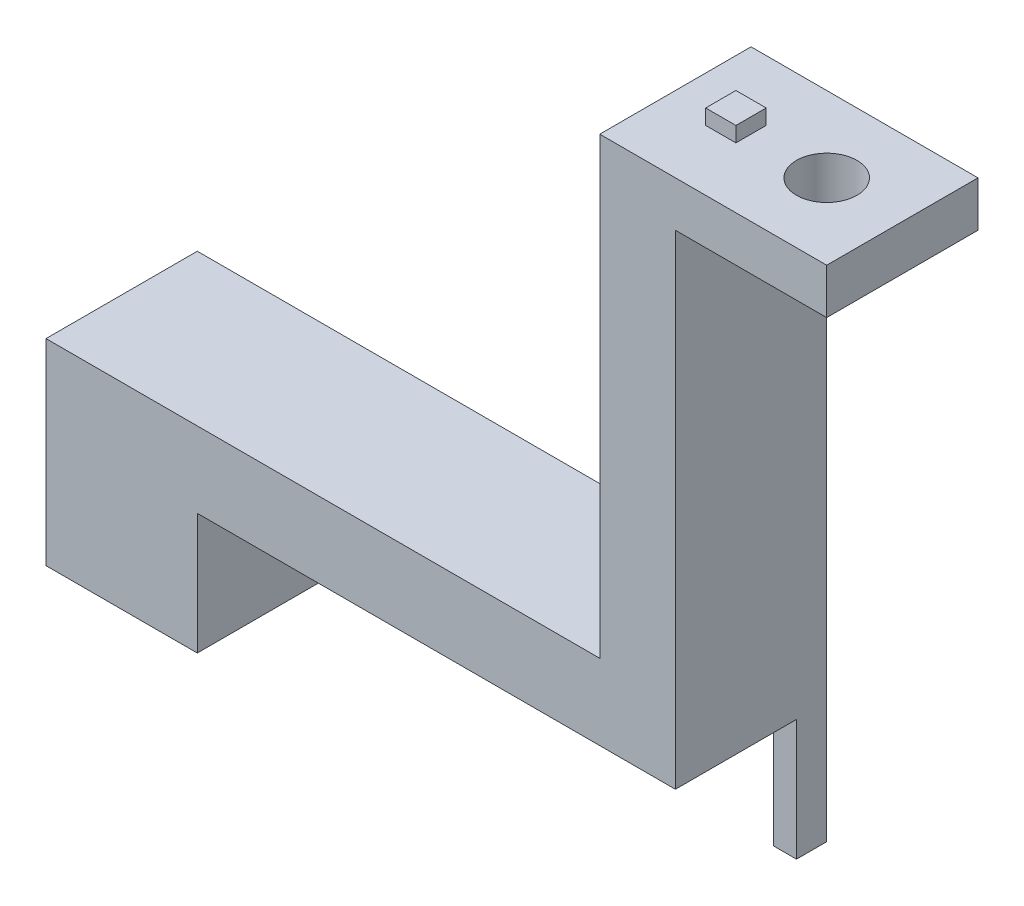
SolidWorks part; units mm, degrees
ref_plane "Front Plane" through (0, 0, 0) normal (0, 0, 1) x (1, 0, 0)
ref_plane "Top Plane" through (0, 0, 0) normal (0, 1, 0) x (1, 0, 0)
ref_plane "Right Plane" through (0, 0, 0) normal (1, 0, 0) x (0, 0, -1)
sketch "Sketch1" plane through (0, 0, 0) normal (0, 0, 1) x (1, 0, 0)
  line L0 (0, 8.6428) -> (0, -8.815) construction
  line L1 (-7.8399, 0) -> (7.1786, 0) construction
  line L2 (36.6, -2.7124) -> (36.6, 24.7717) construction
  line L3 (-5.2779, 43) -> (40.9314, 43) construction
  line L4 (10, 13) -> (36.6, 13)
  line L5 (0, 13) -> (10, 13)
  line L6 (0, 13) -> (0, 0)
  line L7 (0, 0) -> (10, 0)
  line L8 (10, 8) -> (10, 0)
  line L9 (36.6, 13) -> (36.6, 43)
  line L11 (41.6, 40) -> (41.6, 8)
  line L12 (41.6, 8) -> (10, 8)
  line L13 (41.6, 40) -> (51.6, 40)
  line L14 (51.6, 40) -> (51.6, 43)
  line L16 (36.6, 43) -> (51.6, 43)
  dimension "D4" = 30
  dimension "D1" = 36.6
  dimension "D2" = 10
  dimension "D3" = 13
  dimension "D5" = 15
  dimension "D6" = 5
  dimension "D7" = 5
  dimension "D8" = 3
  dimension "D9" = 8
extrude "Boss-Extrude1" add sketch "Sketch1" along normal blind 10
sketch "Sketch2" plane through (0, 0, 0) normal (0, -1, 0) x (1, 0, 0)
  line L0 (5, 15.6268) -> (5, -4.9051) construction
  line L1 (2.45, 6.55) -> (7.55, 6.55)
  line L2 (2.45, 6.55) -> (2.45, 3.45)
  line L3 (2.45, 3.45) -> (7.55, 3.45)
  line L4 (7.55, 6.55) -> (7.55, 3.45)
  line L5 (-4.1598, 5) -> (14.1324, 5) construction
  line L11 (0, 0) -> (10, 0) construction
  line L12 (0, 10) -> (0, 0) construction
  dimension "D1" = 5
  dimension "D2" = 5
  dimension "D3" = 5.1
  dimension "D4" = 3.1
extrude "Cut-Extrude1" cut sketch "Sketch2" against normal blind 10 contours L2 L1 L4 L3
sketch "Sketch3" plane through (0, 43, 0) normal (0, 1, 0) x (1, 0, 0)
  line L0 (29.4648, -5) -> (60.8247, -5) construction
  line L3 (51.6, 0) -> (36.6, 0) construction
  line L4 (51.6, -10) -> (51.6, 0) construction
  line L6 (39.6, -6) -> (41.6, -6)
  line L7 (39.6, -6) -> (39.6, -4)
  line L8 (39.6, -4) -> (41.6, -4)
  line L9 (41.6, -6) -> (41.6, -4)
  circle A0 centre (46.6, -5) radius 2
  dimension "D2" = 4
  dimension "D3" = 3
  dimension "D1" = 5
  dimension "D4" = 2
  dimension "D5" = 2
  dimension "D6" = 3
extrude "Boss-Extrude2" add sketch "Sketch3" along normal blind 1 contours L7 L6 L9 L8
sketch "Sketch11" plane through (0, 43, 0) normal (0, 1, 0) x (1, 0, 0)
  line L0 (29.4648, -5) -> (60.8247, -5) construction
  line L2 (51.6, -10) -> (51.6, 0) construction
  line L5 (39.6, -6) -> (41.6, -6) construction
  line L6 (39.6, -6) -> (41.6, -6)
  line L7 (39.6, -6) -> (39.6, -4)
  line L8 (39.6, -4) -> (41.6, -4)
  line L9 (41.6, -6) -> (41.6, -4)
  circle A0 centre (46.6, -5) radius 2
  dimension "D2" = 4
  dimension "D3" = 0
  dimension "D1" = 3
  dimension "D4" = 2
  dimension "D5" = 2
  dimension "D6" = 3
extrude "Cut-Extrude4" cut sketch "Sketch11" against normal up to next contours A0
sketch "Sketch12" plane through (0, 8, 0) normal (0, -1, 0) x (1, 0, 0)
  line L0 (10, 0) -> (41.6, 0) construction
  line L1 (41.6, 2) -> (40.1, 2)
  line L2 (41.6, 2) -> (41.6, 0)
  line L3 (41.6, 0) -> (40.1, 0)
  line L4 (40.1, 2) -> (40.1, 0)
  line L5 (41.6, 10) -> (41.6, 0) construction
  line L6 (60.8694, 4.3561) -> (126.3325, 4.3561)
  dimension "D1" = 1.5
  dimension "D2" = 2
extrude "Boss-Extrude4" add sketch "Sketch12" along normal blind 8 contours L1 L4 L0 L5 region at (40.85, 8, 1)
